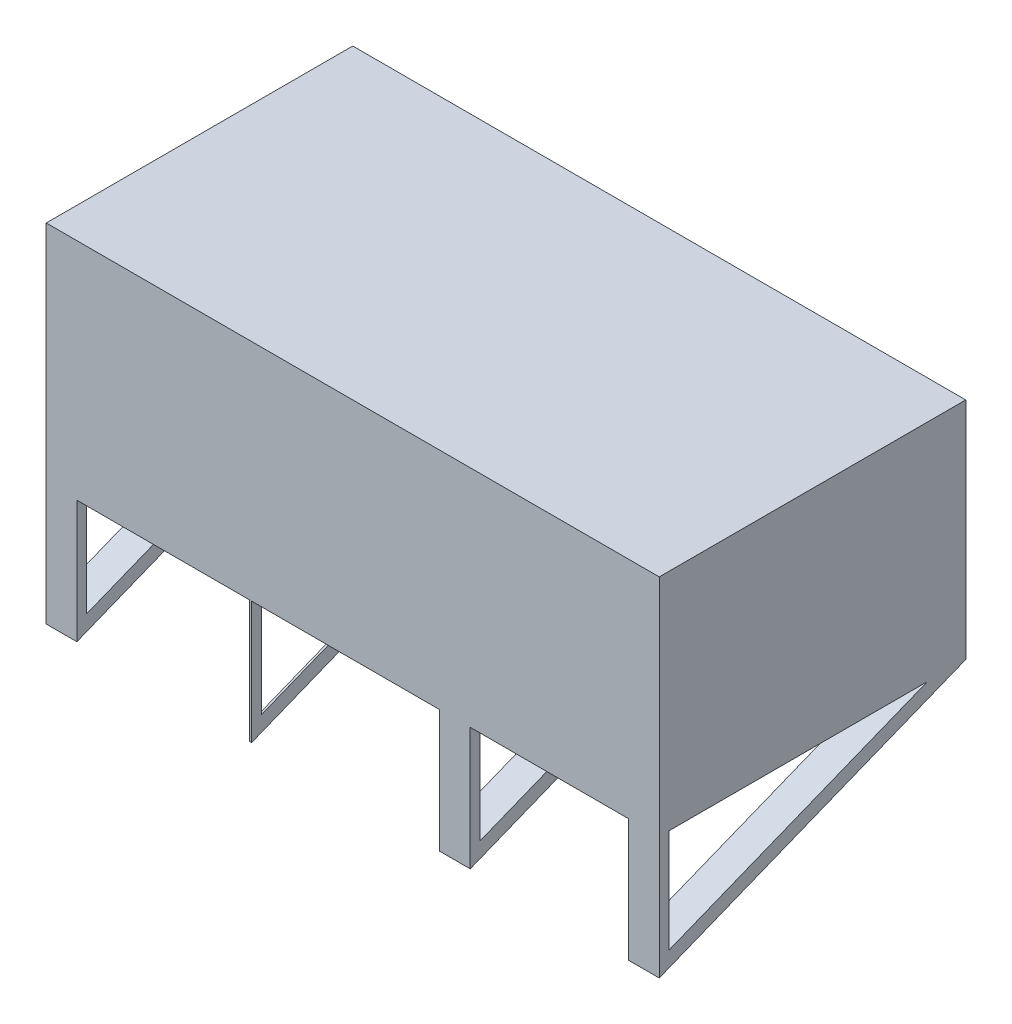
SolidWorks part; units mm, degrees
ref_plane "Front Plane" through (0, 0, 0) normal (0, 0, 1) x (1, 0, 0)
ref_plane "Top Plane" through (0, 0, 0) normal (0, 1, 0) x (1, 0, 0)
ref_plane "Right Plane" through (0, 0, 0) normal (1, 0, 0) x (0, 0, -1)
sketch "LeftSideSketch" plane through (0, 0, 0) normal (1, 0, 0) x (0, 0, -1)
  line L0 (0, 0) -> (150, 0)
  line L1 (150, 0) -> (150, -110)
  line L3 (0, -110) -> (0, 0)
  line L5 (5, -5) -> (5, -105)
  line L6 (5, -105) -> (145, -105)
  line L7 (145, -105) -> (145, -5)
  line L9 (5, -5) -> (145, -5)
  line L10 (0, -110) -> (0, -170)
  line L11 (0, -170) -> (150, -110)
  line L12 (4.8121, -110) -> (4.8121, -160.5359)
  line L13 (4.8121, -160.5359) -> (131.1519, -110)
  line L15 (0, -110) -> (4.8121, -110)
  line L16 (4.8121, -110) -> (131.1519, -110)
  line L17 (131.1519, -110) -> (150, -110)
  dimension "D1" = 150
  dimension "D2" = 110
  dimension "D3" = 5
  dimension "D4" = 5
  dimension "D5" = 5
  dimension "D6" = 5
  dimension "D7" = 7
  dimension "D8" = 4.8121
  dimension "D10" = 60
extrude "walls" add sketch "LeftSideSketch" along normal blind 300 contours L3 L1 L0 L5 L9 L7 L6 region at (0, -1.8601, -75)
extrude "leg1" add sketch "LeftSideSketch<4>" along normal blind 15 contours L10 L11 L13 L12 region at (0, -111.6155, -2.406)
sketch "LeftSideSketch<4>" plane through (0, 0, 0) normal (1, 0, 0) x (0, 0, -1) same geometry as "LeftSideSketch"
extrude "leg4" add sketch "LeftSideSketch<5>" against normal blind 15 from surface contours L10 L11 L13 L12 region at (0, -111.6155, -2.406) starting at face at (300, -55, -75)
sketch "LeftSideSketch<5>" plane through (0, 0, 0) normal (1, 0, 0) x (0, 0, -1) same geometry as "LeftSideSketch"
ref_plane "refPlane1" through (100, 0, 0) normal (1, 0, 0) x (0, 0, -1)
ref_plane "refPlane2" through (200, 0, 0) normal (1, 0, 0) x (0, 0, -1)
extrude "leg2" add sketch "LeftSideSketch<7>" along normal mid plane 1 from surface contours L17 L13 L12 L15 L10 L11 region at (0, -111.6155, -2.406) starting at plane "refPlane1"
sketch "LeftSideSketch<7>" plane through (0, 0, 0) normal (1, 0, 0) x (0, 0, -1) same geometry as "LeftSideSketch"
extrude "leg3" add sketch "LeftSideSketch<9>" along normal mid plane 15 from surface contours L17 L13 L12 L15 L10 L11 region at (0, -111.6155, -2.406) starting at plane "refPlane2"
sketch "LeftSideSketch<9>" plane through (0, 0, 0) normal (1, 0, 0) x (0, 0, -1) same geometry as "LeftSideSketch"
extrude "right wall" add sketch "LeftSideSketch<10>" along normal blind 5 contours L9 L5 L6 L7 region at (0, -55, -75)
sketch "LeftSideSketch<10>" plane through (0, 0, 0) normal (1, 0, 0) x (0, 0, -1) same geometry as "LeftSideSketch"
extrude "left wall" add sketch "LeftSideSketch<11>" against normal blind 5 from surface contours L9 L5 L6 L7 region at (0, -55, -75) starting at face at (300, -126.8453, -46.9254)
sketch "LeftSideSketch<11>" plane through (0, 0, 0) normal (1, 0, 0) x (0, 0, -1) same geometry as "LeftSideSketch"
sketch "TableSketch" plane through (0, -105, 0) normal (0, 1, 0) x (1, 0, 0)
  line L0 (45, 100) -> (45, 35)
  line L1 (45, 35) -> (205, 35)
  line L2 (205, 35) -> (205, 100)
  line L3 (45, 100) -> (205, 100)
  line L4 (182.75, 100) -> (182.75, 88.75)
  line L5 (182.75, 88.75) -> (195, 88.75)
  line L6 (195, 88.75) -> (195, 46.25)
  line L7 (195, 46.25) -> (152.5, 46.25)
  line L8 (152.5, 46.25) -> (152.5, 88.75)
  line L9 (152.5, 88.75) -> (164.75, 88.75)
  line L10 (164.75, 88.75) -> (164.75, 100)
  line L12 (205, 35) -> (142.5, 35)
  line L13 (205, 35) -> (205, 100)
  line L14 (205, 100) -> (142.5, 100)
  line L15 (142.5, 35) -> (142.5, 100)
  line L16 (295, 5) -> (5, 5) construction
  line L18 (295, 145) -> (295, 5) construction
  circle A0 centre (83.75, 67.5) radius 27
  circle A1 centre (83.75, 67.5) radius 19.2
  circle A3 centre (83.4883, 44.4015) radius 3.9
  circle A4 centre (67.2344, 51.4926) radius 3.9
  circle A5 centre (60.7554, 68) radius 3.9
  circle A6 centre (67.8466, 84.2538) radius 3.9 [skipped]
  circle A7 centre (84.354, 90.7328) radius 3.9 [skipped]
  circle A8 centre (100.6078, 83.6417) radius 3.9 [skipped]
  circle A9 centre (107.0868, 67.1343) radius 3.9
  circle A10 centre (99.9957, 50.8805) radius 3.9
  circle A11 centre (83.75, 67.5) radius 3.175
  circle A12 centre (83.75, 67.5) radius 1.685
  point P17 (173.75, 67.5)
  point P20 (152.5, 67.5)
  dimension "D7" = 38.4
  dimension "D13" = 54
  dimension "D14" = 8
  dimension "D15" = 90
  dimension "D17" = 32.5
  dimension "D18" = 23
  dimension "D21" = 6.35
  dimension "D22" = 3.37
  dimension "D1" = 160
  dimension "D2" = 65
  dimension "D3" = 18
  dimension "D4" = 42.5
  dimension "D5" = 12.25
  dimension "D6" = 11.25
  dimension "D8" = 10
  dimension "D9" = 10
  dimension "D10" = 21.25
  dimension "D11" = 21.25
  dimension "D12" = 90
  dimension "D16" = 30
  dimension "D19" = 33
  dimension "D20" = 23
extrude "motor holder" add sketch "TableSketch" against normal blind 33 contours L15 L1 L2 L3 L4 L5 L6 L7 L8 L9 L10 | L13 L12 L15 L14 region at (153.625, -105, -99.0983)
extrude "motor holder2" cut sketch "TableSketch<5>" against normal blind 20 contours L10 L9 L8 L7 L6 L5 L4 L3 region at (173.75, -105, -70.2092)
sketch "TableSketch<5>" plane through (0, -105, 0) normal (0, 1, 0) x (1, 0, 0) same geometry as "TableSketch"
extrude "Cut-Extrude6" cut sketch "TableSketch<7>" against normal blind 1.74 contours A10 A0 A9 A3 A1 A4 A5 | A0 A9 | A0 A10 | A3 | A1 A4 | A1 A5 region at (107.0498, -105, -67.1349) region at (103.1166, -105, -67.1965) region at (100.5811, -105, -83.6161) region at (99.9838, -105, -50.8926) region at (84.3535, -105, -90.716) region at (59.1168, -105, -57.8317) region at (83.4883, -105, -44.4015) region at (67.8466, -105, -84.2538) region at (67.2282, -105, -51.4866) region at (60.7468, -105, -68.0002)
sketch "TableSketch<7>" plane through (0, -105, 0) normal (0, 1, 0) x (1, 0, 0) same geometry as "TableSketch"
extrude "Boss-Extrude10" add sketch "TableSketch<8>" against normal blind 15 from surface contours A0 A9 | A0 A10 | A3 | A1 A4 | A1 A5 region at (107.0498, -105, -67.1349) region at (99.9838, -105, -50.8926) region at (83.4883, -105, -44.4015) region at (67.2282, -105, -51.4866) region at (60.7468, -105, -68.0002) starting at face at (83.75, -106.74, -40.5)
sketch "TableSketch<8>" plane through (0, -105, 0) normal (0, 1, 0) x (1, 0, 0) same geometry as "TableSketch"
extrude "Boss-Extrude11" add sketch "TableSketch<9>" against normal blind 1.5 from surface contours A10 A0 A9 A3 A1 A4 A5 | A1 A5 | A1 A4 | A3 | A0 A10 | A0 A9 region at (107.0498, -105, -67.1349) region at (103.1166, -105, -67.1965) region at (100.5811, -105, -83.6161) region at (99.9838, -105, -50.8926) region at (84.3535, -105, -90.716) region at (59.1168, -105, -57.8317) region at (83.4883, -105, -44.4015) region at (67.8466, -105, -84.2538) region at (67.2282, -105, -51.4866) region at (60.7468, -105, -68.0002) starting at face at (83.4883, -121.74, -40.5015)
sketch "TableSketch<9>" plane through (0, -105, 0) normal (0, 1, 0) x (1, 0, 0) same geometry as "TableSketch"
